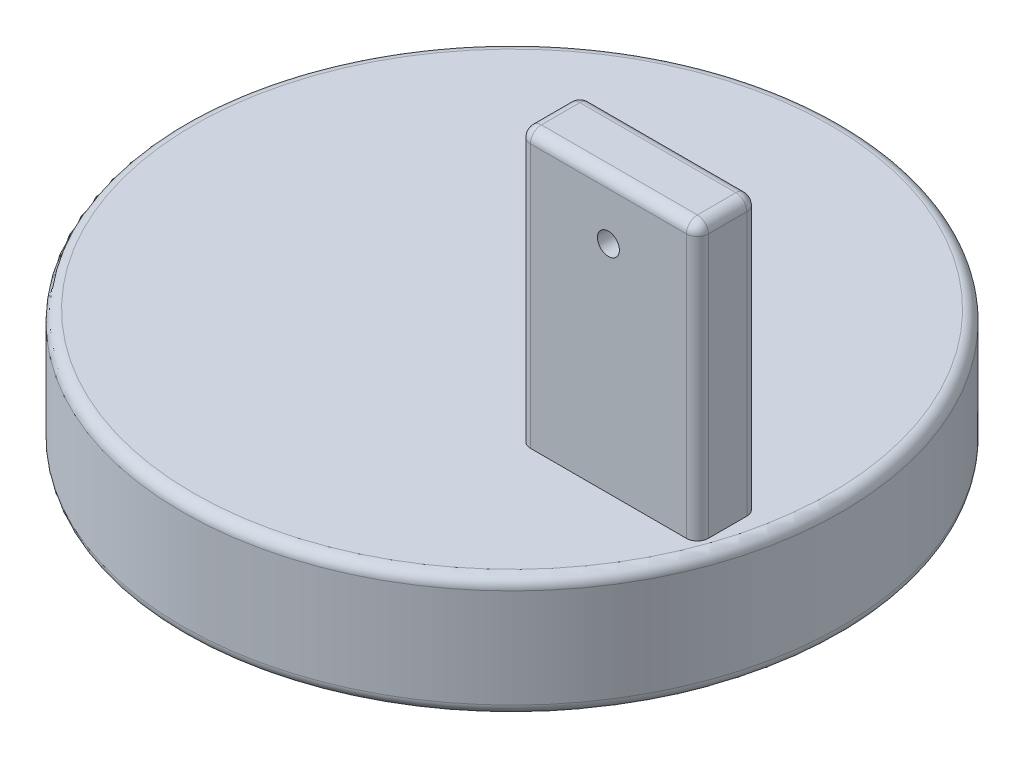
SolidWorks part; units mm, degrees
ref_plane "前视基准面" through (0, 0, 0) normal (0, 0, 1) x (1, 0, 0)
ref_plane "上视基准面" through (0, 0, 0) normal (0, 1, 0) x (1, 0, 0)
ref_plane "右视基准面" through (0, 0, 0) normal (1, 0, 0) x (0, 0, -1)
other "Configuration Table"
sketch "草图2" plane through (0, 0, 0) normal (0, 1, 0) x (1, 0, 0)
  circle A0 centre (0, 0) radius 30
  dimension "D1" = 60
extrude "凸台-拉伸1" add sketch "草图2" along normal blind 11
ref_plane "基准面1" through (0, 0, 4.63) normal (0, 0, 1) x (1, 0, 0)
sketch "草图3" plane through (0, 0, 4.63) normal (0, 0, 1) x (1, 0, 0)
  line L0 (27, 11) -> (27, 36)
  line L1 (30, 11) -> (-30, 11) construction
  line L2 (27, 36) -> (10.8, 36)
  line L3 (10.8, 36) -> (10.8, 11)
  line L4 (30, 0) -> (30, 11) construction
  line L5 (18.9, 54.6324) -> (18.9, 6.7076) construction
  line L6 (27, 11) -> (10.8, 11)
  circle A0 centre (18.9, 30.67) radius 1
  dimension "D2" = 19.67
  dimension "D5" = 2
  dimension "D1" = 25
  dimension "D3" = 3
  dimension "D4" = 16.2
extrude "凸台-拉伸2" add sketch "草图3" along normal blind 5.5
fillet "圆角1" radius 1 10 edges at (10.8, 23.5, 4.63) (27, 23.5, 4.63) (10.8, 23.5, 10.13) (27, 23.5, 10.13) (18.9, 36, 4.63) (18.9, 36, 10.13) (10.8, 36, 7.38) (27, 36, 7.38) (0, 0, 30) (0, 11, 30)
